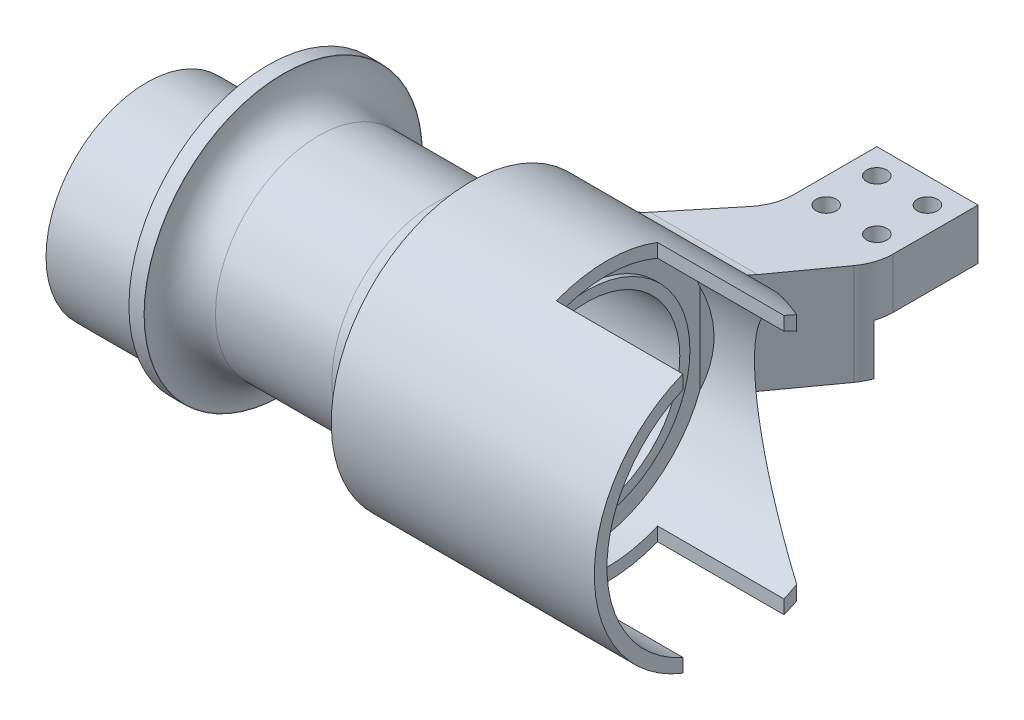
SolidWorks part; units mm, degrees
ref_plane "Alzado" through (0, 0, 0) normal (0, 0, 1) x (1, 0, 0)
ref_plane "Planta" through (0, 0, 0) normal (0, 1, 0) x (1, 0, 0)
ref_plane "Vista lateral" through (0, 0, 0) normal (1, 0, 0) x (0, 0, -1)
sketch "Croquis1" plane through (0, 0, 0) normal (1, 0, 0) x (0, 0, -1)
  circle A0 centre (0, 0) radius 18.4
  circle A1 centre (0, 0) radius 20.4
  dimension "D1" = 36.8
  dimension "D2" = 2
extrude "Saliente-Extruir1" add sketch "Croquis1" along normal blind 60
sketch "Croquis2" plane through (0, 0, 0) normal (-1, 0, 0) x (0, 0, 1)
  line L0 (10.1074, 15.3753) -> (-3.8452, -5.8493) construction
  line L1 (0, 0) -> (0.8977, 15.474) construction
  line L2 (0.8977, 15.474) -> (13.8497, 6.9596) construction
  line L3 (13.8497, 6.9596) -> (12.952, -8.5144) construction
  line L4 (12.952, -8.5144) -> (-0.8977, -15.474) construction
  line L5 (-0.8977, -15.474) -> (-13.8497, -6.9596) construction
  line L6 (-13.8497, -6.9596) -> (-12.952, 8.5144) construction
  line L7 (-12.952, 8.5144) -> (0.8977, 15.474) construction
  line L8 (-12.952, 8.5144) -> (0, 0) construction
  line L9 (0, 0) -> (13.8497, 6.9596) construction
  line L10 (12.952, -8.5144) -> (0, 0) construction
  line L11 (0, 0) -> (-13.8497, -6.9596) construction
  line L12 (-0.8977, -15.474) -> (0, 0) construction
  line L13 (6.9883, -0.4054) -> (13.4009, -0.7774) construction
  line L20 (0, 0) -> (0, -32.026) construction
  circle A8 centre (0.8977, 15.474) radius 1.5
  circle A9 centre (-12.952, 8.5144) radius 1.5
  circle A13 centre (-13.8497, -6.9596) radius 1.5
  circle A14 centre (0, 0) radius 27.5
  arc A15 (9.7768, 9.1979) -> (8.6476, -10.2668) centre (0, 0) ccw
  circle A16 centre (6.9883, -0.4054) radius 6.4234
  arc A17 (9.7768, 9.1979) -> (8.6476, -10.2668) centre (6.9883, -0.4054) ccw
  dimension "D1" = 60
  dimension "D2" = 6.4234
  dimension "D3" = 25.4
  dimension "D4" = 3
  dimension "D9" = 7
  dimension "D10" = 55
  dimension "D11" = 20
  dimension "D5" = 60
  dimension "D6" = 60
  dimension "D7" = 60
  dimension "D8" = 60
extrude "Saliente-Extruir2" add sketch "Croquis2" along normal blind 3
sketch "Croquis15" plane through (-3, 0, 0) normal (-1, 0, 0) x (0, 0, 1)
  line L0 (21.3883, -0.4054) -> (26.3883, -0.4054) construction
  line L1 (6.9883, 18.9946) -> (6.9883, 13.9946)
  line L2 (6.9883, -14.8054) -> (6.9883, -19.8054)
  arc A0 (6.9883, -14.8054) -> (6.9883, 13.9946) centre (6.9883, -0.4054) ccw
  arc A1 (6.9883, -19.8054) -> (6.9883, 18.9946) centre (6.9883, -0.4054) ccw
  dimension "D1" = 28.8
  dimension "D2" = 5
extrude "Saliente-Extruir5" add sketch "Croquis15" along normal blind 10
sketch "Croquis16" plane through (-3, 0, 0) normal (-1, 0, 0) x (0, 0, 1)
  circle A0 centre (6.9883, -0.4054) radius 19.9
  circle A1 centre (6.9883, -0.4054) radius 14.4
  dimension "D1" = 39.8
extrude "Saliente-Extruir6" add sketch "Croquis16" along normal blind 17
sketch "Croquis17" plane through (-3, 0, 0) normal (1, 0, 0) x (0, 0, -1)
  circle A0 centre (-6.9883, -0.4054) radius 13
  circle A1 centre (-6.9883, -0.4054) radius 15
  dimension "D1" = 26
  dimension "D2" = 30
extrude "Saliente-Extruir7" add sketch "Croquis17" against normal blind 2
sketch "Croquis9" plane through (0, 0, 0) normal (0, -1, 0) x (1, 0, 0)
  line L0 (73.6502, -43.6934) -> (73.6502, -63.6934)
  line L1 (73.6502, -63.6934) -> (53.6502, -63.6934)
  line L2 (53.6502, -63.6934) -> (53.6502, -43.6934)
  line L5 (73.6502, -43.6934) -> (59, -23.4)
  line L7 (59, -23.4) -> (37, -23.4)
  line L8 (37, -23.4) -> (53.6502, -43.6934)
  line L9 (73.6502, -43.6934) -> (53.6502, -63.6934) construction
  line L10 (73.6502, -63.6934) -> (53.6502, -43.6934) construction
  circle A0 centre (58.6502, -48.6934) radius 2
  circle A2 centre (58.6502, -58.6934) radius 2
  circle A3 centre (68.6502, -58.6934) radius 2
  circle A4 centre (68.6502, -48.6934) radius 2
  point P10 (63.6502, -53.6934)
  dimension "D6" = 4
  dimension "D1" = 20
  dimension "D2" = 20
  dimension "D3" = 20
  dimension "D4" = 22
  dimension "D7" = 5
extrude "Saliente-Extruir3" add sketch "Croquis9" along normal mid plane 20 separate body
fillet "Redondeo3" radius 10 2 edges at (53.6502, 0, -43.6934) (73.6502, 0, -43.6934)
sketch "Croquis10" plane through (0, -10, 0) normal (0, -1, 0) x (1, 0, 0)
  line L0 (73.6502, -63.6934) -> (73.6502, -46.9258) construction
  line L4 (73.6502, -43.6934) -> (73.6502, -63.6934)
  line L5 (73.6502, -43.6934) -> (51.6502, -43.6934)
  line L6 (51.6502, -43.6934) -> (51.6502, -63.6934)
  line L7 (53.6502, -63.6934) -> (73.6502, -63.6934) construction
  line L8 (51.6502, -63.6934) -> (73.6502, -63.6934)
  point P0 (63.6502, -53.6934)
  dimension "D1" = 20
  dimension "D2" = 22
extrude "Cortar-Extruir3" cut sketch "Croquis10" against normal blind 10
ref_plane "Plano1" through (37, 0, 0) normal (1, 0, 0) x (0, 0, -1)
sketch "Croquis11" plane through (37, 0, 0) normal (1, 0, 0) x (0, 0, -1)
  circle A1 centre (0, 0) radius 27.5
  circle A2 centre (0, 0) radius 20
  dimension "D1" = 40
  dimension "D2" = 55
extrude "Saliente-Extruir4" add sketch "Croquis11" along normal blind 22
sketch "Croquis18" plane through (59, 0, 0) normal (1, 0, 0) x (0, 0, -1)
  circle A0 centre (0, 0) radius 27.5
  circle A1 centre (0, 0) radius 25
  dimension "D1" = 55
  dimension "D2" = 50
extrude "Saliente-Extruir8" add sketch "Croquis18" along normal blind 30
fillet "Redondeo4" radius 7 5 edges at (40.3639, 0, -27.5) (49.71, 10, -25.6174) (49.71, -10, -25.6174) (0, 0, -20.4) (37, 0, -20.4)
sketch "Croquis19" plane through (77.7427, 0, -1000) normal (0, 1, 0) x (1, 0, 0)
  line L0 (11.2573, -972.5) -> (11.2573, -987.5)
  line L1 (11.2573, -1027.5) -> (11.2573, -972.5) construction
  line L2 (11.2573, -987.5) -> (-13.7427, -972.5)
  line L3 (11.2573, -972.5) -> (-15.7829, -972.5) construction
  line L4 (-13.7427, -972.5) -> (11.2573, -972.5)
  line L5 (11.2573, -990) -> (-13.7427, -990)
  line L6 (-13.7427, -990) -> (-13.7427, -1010)
  line L7 (-13.7427, -1010) -> (11.2573, -1010)
  line L8 (11.2573, -1010) -> (11.2573, -1000)
  line L9 (11.2573, -1000) -> (11.2573, -990)
  dimension "D1" = 25
  dimension "D2" = 15
  dimension "D3" = 20
extrude "Cortar-Extruir4" cut sketch "Croquis19" against normal through all both and the other way through all
